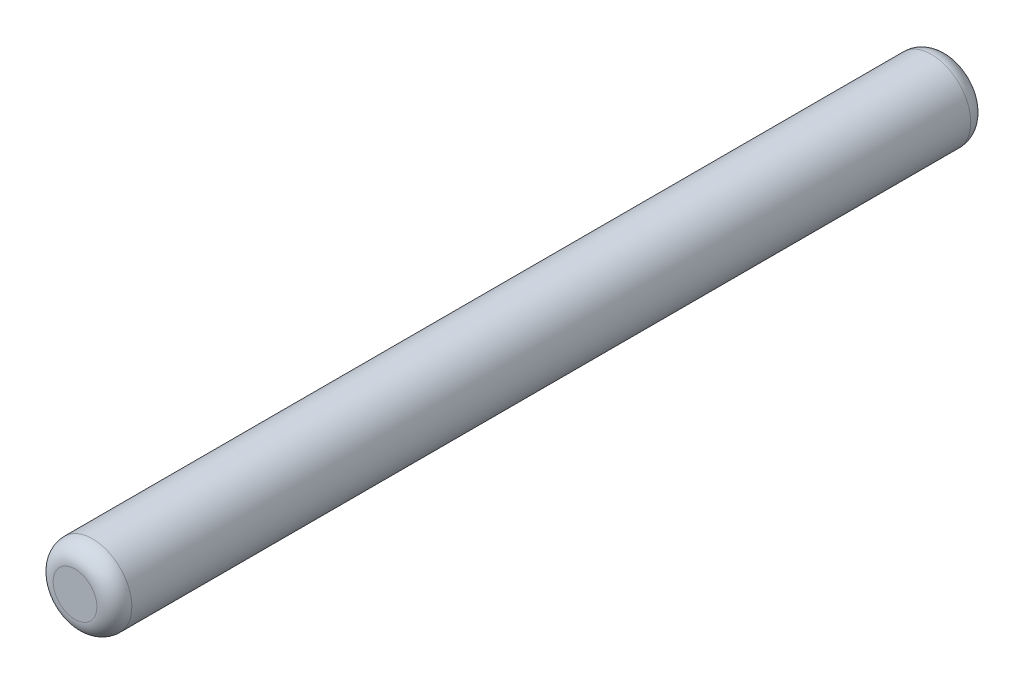
SolidWorks part; units mm, degrees
ref_plane "정면" through (0, 0, 0) normal (0, 0, 1) x (1, 0, 0)
ref_plane "윗면" through (0, 0, 0) normal (0, 1, 0) x (1, 0, 0)
ref_plane "우측면" through (0, 0, 0) normal (1, 0, 0) x (0, 0, -1)
sketch "스케치1" plane through (0, 0, 0) normal (0, 0, 1) x (1, 0, 0)
  circle A0 centre (0, 0) radius 1.8
  dimension "D1" = 3.6
extrude "보스-돌출1" add sketch "스케치1" along normal blind 40
fillet "필렛1" radius 0.8 2 edges at (1.8, 0, 0) (1.8, 0, 40)
